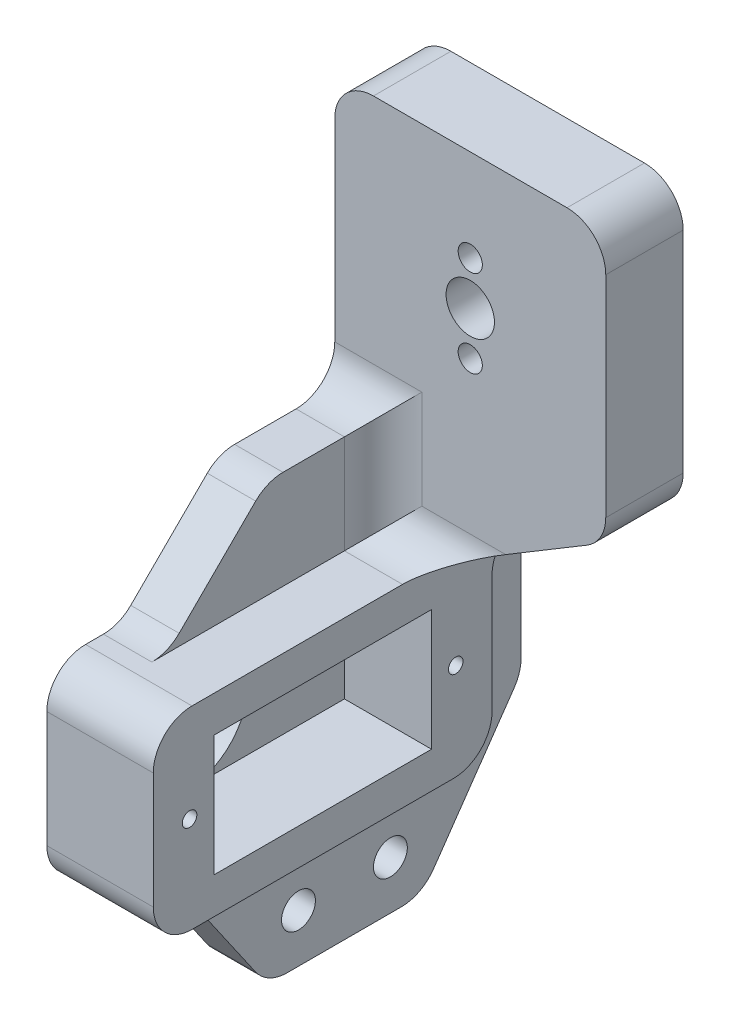
SolidWorks part; units mm, degrees
ref_plane "Front Plane" through (0, 0, 0) normal (1, 0, 0) x (0, 1, 0)
ref_plane "Top Plane" through (0, 0, 0) normal (0, 0, 1) x (0, 1, 0)
ref_plane "Right Plane" through (0, 0, 0) normal (0, 1, 0) x (-1, 0, 0)
sketch "Sketch1" plane through (0, 0, 0) normal (1, 0, 0) x (0, 1, 0)
  line L0 (10, -18.25) -> (-10, -18.25)
  line L2 (-10, -18.25) -> (-24.7965, -8)
  line L4 (-24.7965, -8) -> (-24.7965, 8)
  line L5 (-24.7965, 8) -> (-10, 18.25)
  line L8 (-10, 18.25) -> (-10, 25.75)
  line L9 (-10, 25.75) -> (10, 25.75)
  line L10 (10, 25.75) -> (10, 18.25)
  line L12 (-10, 18.25) -> (10, 18.25) construction
  line L13 (-24.7965, 0) -> (20.2035, 0) construction
  line L14 (20.2035, 8) -> (20.2035, -8)
  line L15 (10, 18.25) -> (20.2035, 8)
  line L16 (10, -18.25) -> (20.2035, -8)
  point P3 (0, -18.25)
  point P14 (20.2035, 0)
  dimension "D1" = 20
  dimension "D2" = 18
  dimension "D3" = 16
  dimension "D4" = 18
  dimension "D5" = 20
  dimension "D6" = 7.5
  dimension "D7" = 7.5
  dimension "D8" = 44
  dimension "D9" = 45
extrude "Boss-Extrude1" add sketch "Sketch1" along normal blind 5
sketch "Sketch2" plane through (5, 0, 0) normal (1, 0, 0) x (0, 1, 0)
  line L0 (10, 18.25) -> (10, 25.75) construction
  line L1 (-10, 25.75) -> (10, 25.75)
  line L2 (-10, 25.75) -> (-10, -9.25)
  line L3 (-10, -9.25) -> (10, -9.25)
  line L4 (10, 25.75) -> (10, -9.25)
  line L5 (0, 25.75) -> (0, -9.25) construction
  line L6 (-10, 8.25) -> (10, 8.25) construction
  line L8 (6.25, -3) -> (-6.25, -3)
  line L9 (6.25, -3) -> (6.25, 19.5)
  line L10 (6.25, 19.5) -> (-6.25, 19.5)
  line L11 (-6.25, -3) -> (-6.25, 19.5)
  line L12 (6.25, -3) -> (-6.25, 19.5) construction
  line L13 (6.25, 19.5) -> (-6.25, -3) construction
  point P11 (0, 8.25)
  dimension "D1" = 35
  dimension "D2" = 22.5
  dimension "D3" = 12.5
extrude "Boss-Extrude2" add sketch "Sketch2" along normal blind 6
extrude "Cut-Extrude1" cut sketch "Sketch2<3>" against normal blind 3 contours L11 L8 L9 L10 region at (5, 0, 8.25)
sketch "Sketch2<3>" plane through (5, 0, 0) normal (1, 0, 0) x (0, 1, 0) same geometry as "Sketch2"
ref_plane "Plane1" through (0, 0, -8) normal (0, 0, 1) x (-1, 0, 0)
sketch "Sketch3" plane through (2, 0, 0) normal (1, 0, 0) x (0, 1, 0)
  line L0 (6.25, 19.5) -> (-6.25, 19.5) construction
  line L1 (6.25, -3) -> (6.25, 19.5) construction
  circle A0 centre (0, 13.25) radius 6.25
  dimension "D1" = 12.5
extrude "Cut-Extrude2" cut sketch "Sketch3" against normal through all
sketch "Sketch4" plane through (0, 0, -8) normal (0, 0, 1) x (-1, 0, 0)
  line L2 (0, -20.2035) -> (0, -48.2035)
  line L3 (0, -48.2035) -> (-28, -48.2035)
  line L4 (-28, -20.2035) -> (-28, -48.2035)
  line L5 (0, -20.2035) -> (0, -10) construction
  line L8 (-28, -20.2035) -> (-11, -10)
  line L9 (-11, -10) -> (-5, -10)
  line L10 (-5, -10) -> (0, -10)
  line L11 (0, -10) -> (0, -20.2035)
  dimension "D1" = 28
  dimension "D2" = 28
  dimension "D3" = 19.827
extrude "Boss-Extrude3" add sketch "Sketch4" along normal mid plane 8
sketch "Sketch5" plane through (0, 0, -4) normal (0, 0, 1) x (1, 0, 0)
  line L0 (0, 48.2035) -> (0, 20.2035) construction
  line L1 (28, 48.2035) -> (0, 48.2035) construction
  line L2 (14, 38.7035) -> (14, 29.7035) construction
  line L3 (11.5, 34.2035) -> (16.5, 34.2035) construction
  circle A0 centre (14, 34.2035) radius 2.5
  circle A1 centre (14, 38.7035) radius 1.25
  circle A2 centre (14, 29.7035) radius 1.25
  dimension "D2" = 5
  dimension "D5" = 2.5
  dimension "D1" = 14
  dimension "D3" = 14
  dimension "D4" = 9
extrude "Cut-Extrude3" cut sketch "Sketch5" against normal blind 10
sketch "Sketch6" plane through (0, 0, -12) normal (0, 0, -1) x (1, 0, 0)
  line L0 (11.5, -34.2035) -> (16.5, -34.2035) construction
  line L1 (16.5, -38.7035) -> (11.5, -38.7035)
  line L2 (16.5, -38.7035) -> (16.5, -29.7035)
  line L3 (16.5, -29.7035) -> (11.5, -29.7035)
  line L4 (11.5, -38.7035) -> (11.5, -29.7035)
  line L5 (16.5, -38.7035) -> (11.5, -29.7035) construction
  line L6 (16.5, -29.7035) -> (11.5, -38.7035) construction
  circle A0 centre (14, -34.2035) radius 2.5 construction
  circle A2 centre (14, -29.7035) radius 2.5
  circle A3 centre (14, -38.7035) radius 2.5
  point P0 (14, -34.2035)
  circle M7 centre (14, -29.7035) radius 1.25
  circle M8 centre (14, -38.7035) radius 1.25
  circle M9 centre (14, -34.2035) radius 2.5
extrude "Cut-Extrude4" cut sketch "Sketch6" against normal blind 1.5 contours A3 L2 M9 | A2 L2 M9 | L3 A2 M7 | A2 L3 M9 M7 | A3 L1 M8 M9 | A3 L1 M8 | L4 A3 M9 | A2 L4 M9 region at (14, 41.1476, -12) region at (16.1099, 36.4535, -12) region at (15.875, 38.6486, -12) region at (16.1099, 31.9535, -12) region at (11.8901, 36.4535, -12) region at (16.0718, 31.0021, -12) region at (15.875, 29.6476, -12) region at (11.8901, 31.9535, -12)
fillet "Fillet1" radius 4 18 edges at (5, 15.1017, -4) (8, 10, -4) (2.5, 20.2035, -4) (2.5, 16.2216, -12) (2.5, -10, 18.25) (2.5, 10, 18.25) (5.5, 10, 25.75) (5.5, -10, 25.75) (0, 48.2035, -8) (28, 48.2035, -8) (28, 20.2035, -8) (2.5, 20.2035, 8) (2.5, 10, -18.25) (2.5, -10, -18.25) (2.5, -24.7965, 8) (2.5, -24.7965, -8) (8, -10, -9.25) (8, 10, -9.25)
sketch "Sketch7" plane through (5, 0, 0) normal (1, 0, 0) x (0, 1, 0)
  line L0 (-24.7965, 0) -> (20.2035, 0) construction
  line L1 (-24.7965, 5.9049) -> (-24.7965, -5.9049) construction
  line L2 (-19.7965, -4.75) -> (-19.7965, 4.75) construction
  line L3 (0, 25.75) -> (-0.206, -18.25) construction
  line L4 (6, 25.75) -> (-6, 25.75) construction
  line L5 (-8.7499, -18.25) -> (8.3378, -18.25) construction
  circle A0 centre (-19.7965, 4.75) radius 1.75
  circle A1 centre (-19.7965, -4.75) radius 1.75
  circle A2 centre (-0.1826, -13.25) radius 1.75
  point P8 (-19.7965, 0)
  dimension "D3" = 3.5
  dimension "D1" = 3.5
  dimension "9.5" = 9.5
  dimension "D2" = 5
  dimension "D4" = 5
extrude "Cut-Extrude5" cut sketch "Sketch7" against normal through all
sketch "Sketch8" plane through (11, 0, 0) normal (1, 0, 0) x (0, 1, 0)
  line L0 (0, 22) -> (0, -5.5) construction
  line L1 (-6.25, 8.25) -> (6.25, 8.25) construction
  line L2 (-6.25, 19.5) -> (-6.25, -3) construction
  line L3 (6.25, -3) -> (6.25, 19.5) construction
  circle A0 centre (0, 22) radius 0.75
  circle A1 centre (0, -5.5) radius 0.75
  point P10 (0, 8.25)
  dimension "D2" = 1.5
  dimension "D1" = 27.5
extrude "Cut-Extrude6" cut sketch "Sketch8" against normal up to surface (9 mm away) up to face at (2, 4.5981, 17.8481)
